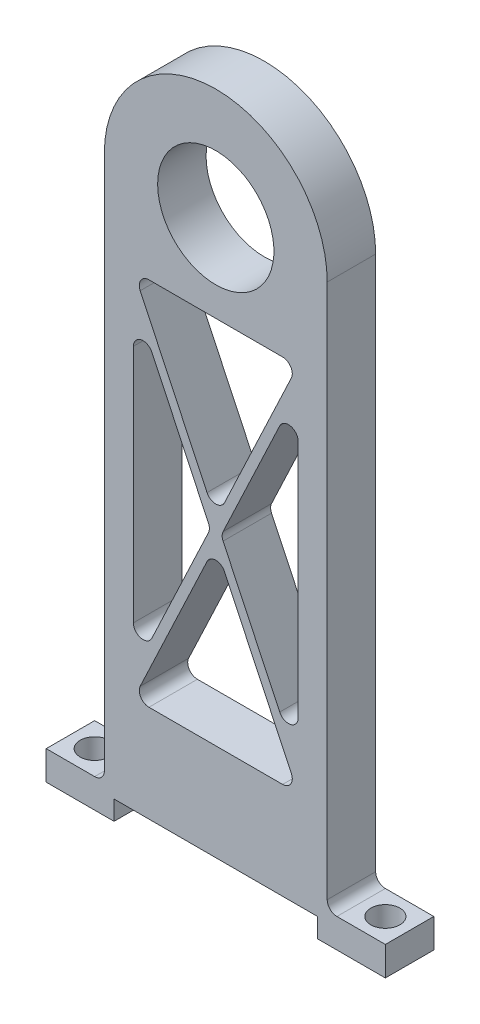
SolidWorks part; units mm, degrees
ref_plane "Front Plane" through (0, 0, 0) normal (0, 0, 1) x (1, 0, 0)
ref_plane "Top Plane" through (0, 0, 0) normal (0, 1, 0) x (1, 0, 0)
ref_plane "Right Plane" through (0, 0, 0) normal (1, 0, 0) x (0, 0, -1)
sketch "Sketch1" plane through (0, 0, 0) normal (0, 1, 0) x (1, 0, 0)
  line L1 (44.45, 6.35) -> (-44.45, 6.35)
  line L2 (44.45, 6.35) -> (44.45, -6.35)
  line L3 (44.45, -6.35) -> (-44.45, -6.35)
  line L4 (-44.45, 6.35) -> (-44.45, -6.35)
  line L5 (44.45, 6.35) -> (-44.45, -6.35) construction
  line L6 (44.45, -6.35) -> (-44.45, 6.35) construction
  line L7 (-38.1, 0) -> (-44.45, 0) construction
  line L8 (38.1, 0) -> (44.45, 0) construction
  circle A0 centre (-38.1, 0) radius 3.81
  circle A1 centre (38.1, 0) radius 3.81
  point P0 (0, 0)
  dimension "D1" = 7.62
  dimension "D2" = 76.2
  dimension "D3" = 88.9
  dimension "D4" = 12.7
extrude "Boss-Extrude1" add sketch "Sketch1" along normal blind 7.62
sketch "Sketch2" plane through (0, 7.62, 0) normal (0, 1, 0) x (1, 0, 0)
  line L0 (44.45, 6.35) -> (-44.45, 6.35) construction
  line L1 (29.21, 6.35) -> (-29.21, 6.35)
  line L2 (29.21, 6.35) -> (29.21, -6.35)
  line L3 (29.21, -6.35) -> (-29.21, -6.35)
  line L4 (-29.21, 6.35) -> (-29.21, -6.35)
  line L5 (29.21, 6.35) -> (-29.21, -6.35) construction
  line L6 (29.21, -6.35) -> (-29.21, 6.35) construction
  point P0 (0, 0)
  dimension "D1" = 58.42
extrude "Boss-Extrude2" add sketch "Sketch2" along normal blind 142.748
sketch "Sketch3" plane through (0, 0, 6.35) normal (0, 0, 1) x (1, 0, 0)
  line L0 (29.21, 150.368) -> (-29.21, 150.368)
  arc A0 (29.21, 150.368) -> (-29.21, 150.368) centre (0, 150.368) ccw
extrude "Boss-Extrude3" add sketch "Sketch3" against normal up to surface (12.7 mm away) contours A0 L0 up to face at (0, 41.402, -6.35)
sketch "Sketch4" plane through (0, 0, -6.35) normal (0, 0, -1) x (-1, 0, 0)
  line L0 (0, 150.368) -> (0, 0) construction
  line L1 (-44.45, 0) -> (44.45, 0) construction
  circle A0 centre (0, 150.368) radius 15.24
  dimension "D1" = 30.48
extrude "Cut-Extrude1" cut sketch "Sketch4" against normal up to surface (12.7 mm away) up to face at (0, 45.0532, 6.35)
sketch "Sketch5" plane through (0, 0, 6.35) normal (0, 0, 1) x (1, 0, 0)
  line L0 (-21.5248, 127.508) -> (21.5248, 127.508)
  line L1 (24.13, 27.94) -> (-24.13, 27.94)
  line L2 (24.13, 27.94) -> (24.13, 130.048)
  line L3 (24.13, 130.048) -> (-24.13, 130.048)
  line L4 (-24.13, 27.94) -> (-24.13, 130.048)
  line L5 (24.13, 27.94) -> (-24.13, 130.048) construction
  line L6 (24.13, 130.048) -> (-24.13, 27.94) construction
  line L7 (21.5248, 127.508) -> (0, 81.9661)
  line L8 (0, 81.9661) -> (-21.5248, 127.508)
  line L9 (-21.59, 121.7018) -> (-1.4047, 78.994)
  line L10 (-1.4047, 78.994) -> (-21.59, 36.2862)
  line L11 (-21.59, 36.2862) -> (-21.59, 121.7018)
  line L12 (0, 76.0219) -> (-21.5248, 30.48)
  line L13 (-21.5248, 30.48) -> (21.5248, 30.48)
  line L14 (21.5248, 30.48) -> (0, 76.0219)
  line L15 (21.59, 121.7018) -> (21.59, 36.2862)
  line L16 (21.59, 36.2862) -> (1.4047, 78.994)
  line L17 (1.4047, 78.994) -> (21.59, 121.7018)
  line L18 (-24.13, 78.994) -> (-21.59, 78.994) construction
  line L19 (24.13, 78.994) -> (21.59, 78.994) construction
  line L20 (0, 30.48) -> (0, 27.94) construction
  line L21 (0, 130.048) -> (0, 127.508) construction
  line L22 (-44.45, 0) -> (44.45, 0) construction
  line L23 (26.67, 5.08) -> (-26.67, 5.08)
  line L24 (26.67, 5.08) -> (26.67, 0)
  line L25 (26.67, 0) -> (-26.67, 0)
  line L26 (-26.67, 5.08) -> (-26.67, 0)
  line L27 (26.67, 5.08) -> (-26.67, 0) construction
  line L28 (26.67, 0) -> (-26.67, 5.08) construction
  line L29 (-29.21, 150.368) -> (-29.21, 7.62) construction
  line L30 (29.21, 150.368) -> (29.21, 7.62) construction
  line L31 (-29.21, 78.994) -> (-24.13, 78.994) construction
  line L32 (24.13, 78.994) -> (29.21, 78.994) construction
  circle A0 centre (0, 150.368) radius 15.24 construction
  point P0 (0, 78.994)
  point P23 (0, 2.54)
  point P38 (-29.21, 78.994)
  dimension "D7" = 20.32
  dimension "D1" = 2.54
  dimension "D2" = 2.54
  dimension "D3" = 5.08
  dimension "D4" = 2.54
  dimension "D5" = 2.54
  dimension "D6" = 5.08
extrude "Cut-Extrude2" cut sketch "Sketch5" against normal up to next contours L8 L0 L7 | L17 L15 L16 | L12 L13 L14 | L9 L10 L11 | L24 L23 L26 L25
fillet "Fillet1" radius 2.54 2 edges at (29.21, 7.62, 0) (-29.21, 7.62, 0)
fillet "Fillet2" radius 2.54 12 edges at (0, 76.0219, 0) (-1.4047, 78.994, 0) (0, 81.9661, 0) (1.4047, 78.994, 0) (21.59, 36.2862, 0) (21.5248, 30.48, 0) (-21.5248, 30.48, 0) (-21.59, 36.2862, 0) (-21.59, 121.7018, 0) (21.59, 121.7018, 0) (21.5248, 127.508, 0) (-21.5248, 127.508, 0)
